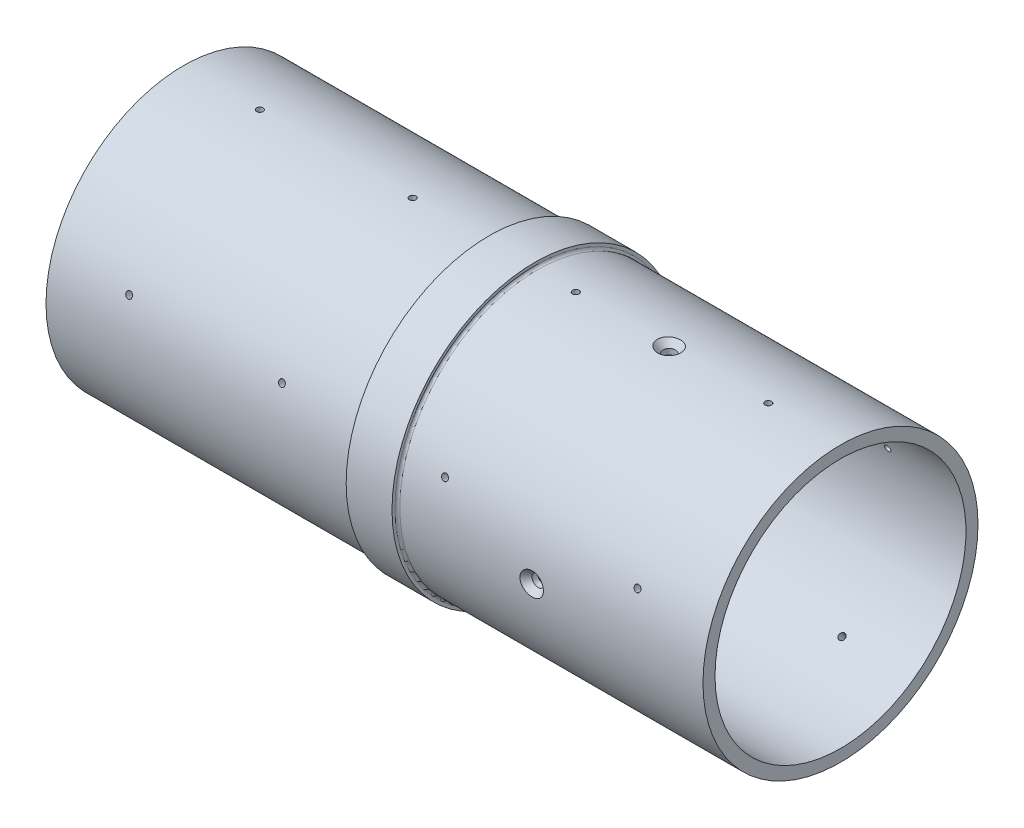
SolidWorks part; units mm, degrees
ref_plane "Front Plane" through (0, 0, 0) normal (0, 0, 1) x (1, 0, 0)
ref_plane "Top Plane" through (0, 0, 0) normal (0, 1, 0) x (1, 0, 0)
ref_plane "Right Plane" through (0, 0, 0) normal (1, 0, 0) x (0, 0, -1)
sketch "Sketch1" plane through (0, 0, 0) normal (0, 1, 0) x (1, 0, 0)
  line L0 (-95.7, 42.15) -> (-105.7, 52.15)
  line L1 (0, -55) -> (0, 55) construction
  line L2 (0, 52.15) -> (-74.2, 52.15)
  line L3 (-76.2, 50.15) -> (-76.2, 42.15)
  line L4 (-76.2, 42.15) -> (-95.7, 42.15)
  line L7 (-273.05, 52.15) -> (-273.05, 57.15)
  line L8 (-273.05, 57.15) -> (-147.05, 57.15)
  line L9 (-146.05, 58.15) -> (-146.05, 59.4)
  line L10 (-146.05, 59.4) -> (-127, 59.4)
  line L11 (-127, 59.4) -> (-127, 58.15)
  line L12 (-126, 57.15) -> (0, 57.15)
  line L13 (0, 57.15) -> (0, 52.15)
  line L14 (-105.7, 52.15) -> (-273.05, 52.15)
  line L15 (-76.2, 50.15) -> (-76.2, 52.15)
  line L16 (-76.2, 52.15) -> (-74.2, 52.15)
  arc A2 (-147.05, 57.15) -> (-146.05, 58.15) centre (-147.05, 58.15) ccw
  arc A3 (-127, 58.15) -> (-126, 57.15) centre (-126, 58.15) ccw
  point P18 (-76.2, 52.15)
  point P21 (-95.7, 52.15)
  point P24 (-146.05, 57.15)
  point P27 (-127, 57.15)
  dimension "D11" = 135
  dimension "D12" = 2.25
  dimension "D13" = 1
  dimension "D1" = 127
  dimension "D2" = 127
  dimension "D3" = 5
  dimension "D4" = 19.05
  dimension "D5" = 76.2
  dimension "D6" = 10
  dimension "D7" = 19.5
  dimension "D8" = 10
  dimension "D9" = 5
  dimension "D10" = 2.25
sketch "Sketch3" plane through (0, 0, 0) normal (0, 1, 0) x (1, 0, 0)
  line L0 (-185.7686, 0) -> (-52.5722, 0)
  line L1 (-150.1775, 0) -> (150.1775, 0) construction
revolve "Revolve1" add sketch "Sketch1" angle 360 about L0
ref_plane "Plane1" through (0, 57.15, 0) normal (0, 1, 0) x (1, 0, 0)
hole_wizard "CSK for #10 Flat Head Machine Screw1" positions "Sketch6" profile "Sketch5" countersink size "#10" standard "ANSI Inch" end condition up to next
sketch "Sketch6" plane through (0, 57.15, 0) normal (0, 1, 0) x (1, 0, 0)
  line L0 (-65.34, 0) -> (65.34, 0) construction
  line L1 (-71.2, 0) -> (0, 0)
  point P0 (-71.2, 0)
  dimension "D1" = 71.2
sketch "Sketch5" plane through (-71.2, 57.15, 0) normal (1, 0, 0) x (0, 0, 1)
  line L0 (0, 0) -> (0, 109.301)
  line L1 (0, 109.301) -> (2.5527, 109.301)
  line L2 (2.5527, 109.301) -> (2.5527, 2.6882)
  line L3 (2.5527, 2.6882) -> (4.8895, 0)
  line L5 (4.8895, 0) -> (0, 0)
  line L6 (-2.5527, 2.6882) -> (-4.8895, 0) construction
  line L11 (0, -6.35) -> (0, 107.95) construction
  dimension "Thru Hole Dia." = 5.1054
  dimension "Thru Hole Depth" = 109.301
  dimension "Near C'Sink Dia." = 9.779
  dimension "Near C'Sink Angle" = 82
hole_wizard "#6-32 Tapped Hole2" positions "Sketch7" profile "Sketch8" tap size "#6-32" standard "ANSI Inch" end condition up to next
sketch "Sketch7" plane through (0, 57.15, 0) normal (0, 1, 0) x (1, 0, 0)
  line L0 (-65.34, 0) -> (65.34, 0) construction
  line L1 (-30, 0) -> (0, 0)
  line L2 (-110, 0) -> (0, 0)
  point P0 (-30, 0)
  point P9 (-110, 0)
  dimension "D1" = 30
  dimension "D2" = 110
sketch "Sketch8" plane through (-30, 57.15, 0) normal (1, 0, 0) x (0, 0, 1)
  line L0 (0, 0) -> (0, 114.3)
  line L1 (0, 114.3) -> (1.3525, 114.3)
  line L2 (1.3525, 114.3) -> (1.3525, 0)
  line L5 (1.3525, 0) -> (0, 0)
  line L11 (0, -6.35) -> (0, 107.95) construction
  dimension "Thru Tap Drill Dia." = 2.7051
  dimension "Thru Tap Drill Depth" = 114.3
cosmetic thread "Hole Thread27" parameters "D2"=3.5052
cosmetic thread "Hole Thread28" parameters "D2"=3.5052
ref_plane "Plane2" through (0, 57.15, 0) normal (0, 1, 0) x (1, 0, 0)
hole_wizard "#6-32 Tapped Hole1" positions "Sketch9" profile "Sketch10" tap size "#6-32" standard "ANSI Inch" end condition up to next
sketch "Sketch9" plane through (0, 57.15, 0) normal (0, 1, 0) x (1, 0, 0)
  line L0 (-65.34, 0) -> (65.34, 0) construction
  line L1 (-241.3, 0) -> (-273.05, 0)
  line L2 (-273.05, 57.15) -> (-273.05, -57.15) construction
  line L4 (-177.8, 0) -> (-273.05, 0)
  point P0 (-241.3, 0)
  point P4 (-177.8, 0)
  dimension "D1" = 31.75
  dimension "D2" = 95.25
sketch "Sketch10" plane through (-241.3, 57.15, 0) normal (1, 0, 0) x (0, 0, 1)
  line L0 (0, 0) -> (0, 114.3)
  line L1 (0, 114.3) -> (1.3525, 114.3)
  line L2 (1.3525, 114.3) -> (1.3525, 0)
  line L5 (1.3525, 0) -> (0, 0)
  line L11 (0, -6.35) -> (0, 107.95) construction
  dimension "Thru Tap Drill Dia." = 2.7051
  dimension "Thru Tap Drill Depth" = 114.3
cosmetic thread "Hole Thread31" parameters "D2"=3.5052
cosmetic thread "Hole Thread32" parameters "D2"=3.5052
chamfer "Chamfer1" distance 1 angle 45 1 edges at (-76.2, 0, 52.15)
pattern_circular "CirPattern1" count 4 over 360 of "CSK for #10 Flat Head Machine Screw1" reverse direction yes
pattern_circular "CirPattern3" count 5 over 360 of "#6-32 Tapped Hole2", "#6-32 Tapped Hole1" reverse direction yes
cosmetic thread "Hole Thread49" parameters "D2"=3.5052
cosmetic thread "Hole Thread50" parameters "D2"=3.5052
cosmetic thread "Hole Thread51" parameters "D2"=3.5052
cosmetic thread "Hole Thread52" parameters "D2"=3.5052
cosmetic thread "Hole Thread53" parameters "D2"=3.5052
cosmetic thread "Hole Thread54" parameters "D2"=3.5052
cosmetic thread "Hole Thread55" parameters "D2"=3.5052
cosmetic thread "Hole Thread56" parameters "D2"=3.5052
cosmetic thread "Hole Thread57" parameters "D2"=3.5052
cosmetic thread "Hole Thread58" parameters "D2"=3.5052
cosmetic thread "Hole Thread59" parameters "D2"=3.5052
cosmetic thread "Hole Thread60" parameters "D2"=3.5052
cosmetic thread "Hole Thread61" parameters "D2"=3.5052
cosmetic thread "Hole Thread62" parameters "D2"=3.5052
cosmetic thread "Hole Thread63" parameters "D2"=3.5052
cosmetic thread "Hole Thread64" parameters "D2"=3.5052
